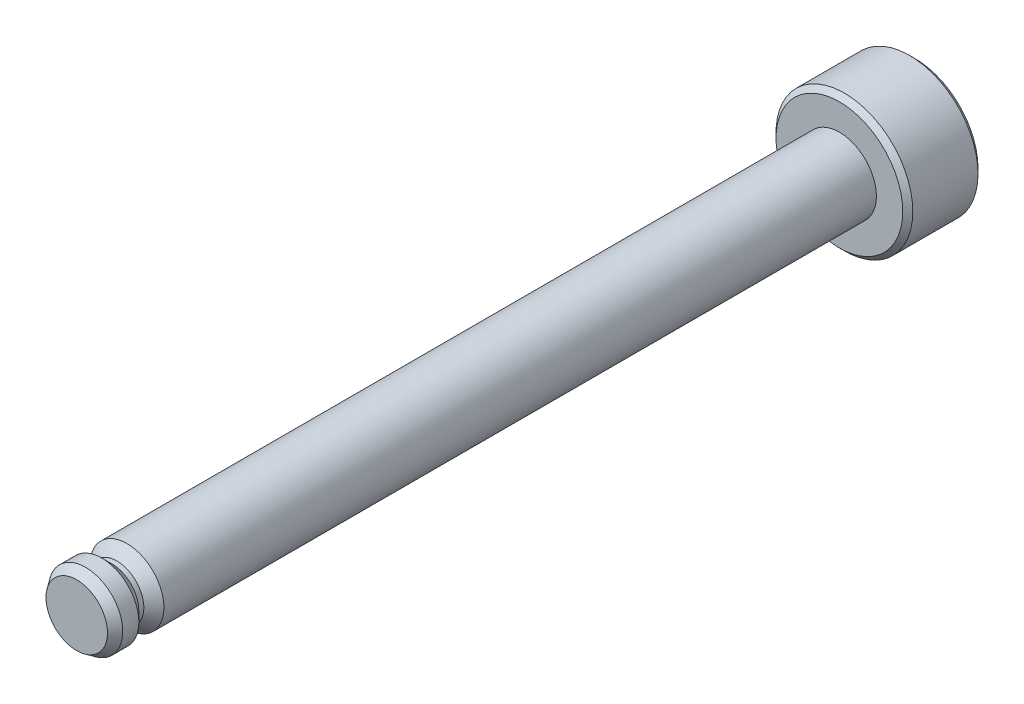
SolidWorks part; units mm, degrees
ref_plane "Front" through (0, 0, 0) normal (0, 0, 1) x (1, 0, 0)
ref_plane "Top" through (0, 0, 0) normal (0, 1, 0) x (1, 0, 0)
ref_plane "Right" through (0, 0, 0) normal (1, 0, 0) x (0, 0, -1)
sketch "Sketch2" plane through (0, 0, 0) normal (0, 0, 1) x (1, 0, 0)
  circle A0 centre (0, 0) radius 1.475
  dimension "D1" = 2.95
extrude "Shaft" add sketch "Sketch2" along normal blind 30.4
sketch "Sketch5" plane through (0, 0, 0) normal (0, 0, 1) x (1, 0, 0)
  circle A0 centre (0, 0) radius 2.725
  dimension "D1" = 5.45
extrude "Head" add sketch "Sketch5" against normal blind 3
chamfer "Chamfer1" distance 0.25 angle 55 1 edges at (1.475, 0, 30.4) first distance on face at (1.475, 0, 30.4)
chamfer "Deburs" distance 0.2 angle 45 2 edges at (2.725, 0, 0) (2.725, 0, -3)
sketch "Sketch6" plane through (0, 0, 0) normal (1, 0, 0) x (0, 0, -1)
  line L0 (0, 0) -> (-28.9, 0) construction
  line L1 (-28.9, 0) -> (-28.9, 1.075) construction
  line L2 (0, 1.475) -> (-30.043, 1.475) construction
  line L3 (-29.4, 1.475) -> (-28.4, 1.475)
  line L4 (-28.4, 1.475) -> (-28.8, 1.075)
  line L5 (-28.8, 1.075) -> (-29, 1.075)
  line L6 (-29, 1.075) -> (-29.4, 1.475)
  line L7 (-28.9, 1.075) -> (-28.9, 1.475) construction
  dimension "D1" = 28.9
  dimension "D2" = 0.4
  dimension "D3" = 1
revolve "e-Clip Notch Long" cut sketch "Sketch6" angle 360 about L0
equation "\"D1@Sketch2\"=\"Plastic Hardware OD@Box Assy.Assembly\""
equation "\"D1\"= \"Countersink Diameter@Box Assy.Assembly\" - .3mm"
equation "\"D1@Head\"=\"Countersink Depth@Box Assy.Assembly\""
equation "\"Length\"= 30mm"
equation "\"D1@Shaft\"=\"Length\"+.4mm"
equation "\"D1@Sketch6\"=\"Length\"-1.1mm"
